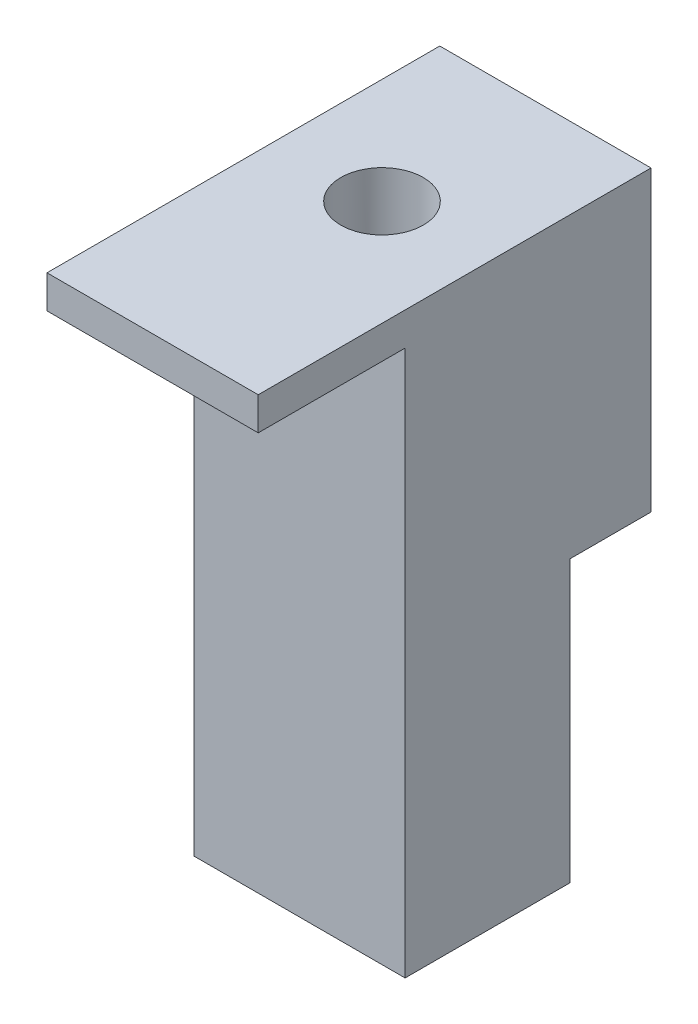
SolidWorks part; units mm, degrees
ref_plane "Front Plane" through (0, 0, 0) normal (0, 0, 1) x (1, 0, 0)
ref_plane "Top Plane" through (0, 0, 0) normal (0, 1, 0) x (1, 0, 0)
ref_plane "Right Plane" through (0, 0, 0) normal (1, 0, 0) x (0, 0, -1)
sketch "Sketch2" plane through (0, 0, 0) normal (0, 0, 1) x (1, 0, 0)
  line L0 (125.75, 12.9444) -> (138.75, 12.9444) construction
  line L5 (125.45, -3.5556) -> (138.75, -3.5556)
  line L6 (138.75, -3.5556) -> (138.75, 35)
  line L7 (138.75, 35) -> (125.75, 35)
  line L8 (125.75, 35) -> (125.75, 5.0019)
  line L9 (125.45, 3.05) -> (125.45, -3.5556)
  line L10 (125.45, -3.5556) -> (138.75, -3.5556) construction
  line L11 (138.75, 12.9444) -> (138.75, 35)
  line L12 (138.75, 35) -> (125.75, 35)
  line L13 (125.75, 35) -> (125.75, 12.9444)
  arc A0 (138.75, 12.9444) -> (125.75, 12.9444) centre (132.25, 12.9444) ccw
  arc A1 (125.75, 5.0019) -> (125.45, 3.05) centre (131.95, 3.05) ccw
  point P8 (132.25, 12.9444)
  dimension "D2" = 16.5
  dimension "D1" = 0
extrude "Boss-Extrude1" add sketch "Sketch2" along normal blind 10
sketch "Sketch3" plane through (0, 35, 0) normal (0, 1, 0) x (1, 0, 0)
  line L0 (138.75, -5) -> (125.75, -5)
  line L1 (138.75, -10) -> (138.75, 0) construction
  line L2 (125.75, -10) -> (125.75, 0) construction
  line L4 (138.75, -5) -> (125.75, -5)
  line L5 (138.75, -5) -> (138.75, -10)
  line L6 (138.75, -10) -> (125.75, -10)
  line L7 (125.75, -5) -> (125.75, -10)
  line M2 (125.75, 0) -> (125.75, -10)
  line M3 (125.75, -10) -> (138.75, -10)
  line M4 (138.75, -10) -> (138.75, 0)
extrude "Boss-Extrude2" add sketch "Sketch3" against normal up to vertex (22.0556 mm away) contours L0 M4 M2 M3 region at (132.25, 35, 7.5) up to point (138.75, 12.9444, 10)
sketch "Sketch4" plane through (0, 35, 0) normal (0, 1, 0) x (1, 0, 0)
  line L0 (125.75, 0) -> (125.75, -24) construction
  line L1 (138.75, -10) -> (125.75, -10)
  line L2 (138.75, -10) -> (138.75, -15)
  line L3 (138.75, -15) -> (125.75, -15)
  line L4 (125.75, -10) -> (125.75, -15)
  dimension "D1" = 5
extrude "Boss-Extrude3" add sketch "Sketch4" against normal up to vertex (22.0556 mm away) up to point (138.75, 12.9444, 10)
sketch "Sketch5" plane through (0, 12.9444, 0) normal (0, -1, 0) x (1, 0, 0)
  line L0 (125.75, 15) -> (138.75, 5) construction
  circle A0 centre (132.25, 10) radius 2.5
  dimension "D1" = 5
extrude "Cut-Extrude1" cut sketch "Sketch5" against normal blind 23
sketch "Sketch6" plane through (0, 12.9444, 0) normal (0, -1, 0) x (1, 0, 0)
  line L0 (138.75, 15) -> (138.75, 5) construction
  line L1 (125.75, 8.5) -> (138.75, 8.5)
  line L2 (125.75, 8.5) -> (125.75, 11.5)
  line L3 (125.75, 11.5) -> (138.75, 11.5)
  line L4 (138.75, 8.5) -> (138.75, 11.5)
  line L5 (125.75, 8.5) -> (138.75, 11.5) construction
  line L6 (125.75, 11.5) -> (138.75, 8.5) construction
  line L7 (127.25, 11.5) -> (127.25, 8.5)
  line L8 (137.25, 11.5) -> (137.25, 8.5)
  point P0 (132.25, 10)
  circle M4 centre (132.25, 10) radius 2.5
  dimension "D1" = 3
  dimension "D2" = 5
  dimension "D3" = 5
extrude "Cut-Extrude2" cut sketch "Sketch6" against normal offset from surface (17.0556 mm away) 5 contours L8 L3 L1 M4 | L3 L7 L1 M4 region at (128.5837, 12.9444, 10) region at (135.9163, 12.9444, 10) up to face at (132.25, 35, 7.5)
sketch "Sketch7" plane through (0, 12.9444, 0) normal (0, -1, 0) x (1, 0, 0)
  line L0 (132.25, 10) -> (132.25, 5)
  line L1 (131, 10) -> (133.5, 10)
  line L2 (131, 5) -> (133.5, 5)
  line L3 (133.5, 10) -> (133.5, 5)
  line L4 (138.75, 5) -> (125.75, 5) construction
  line L5 (131, 10) -> (131, 5)
  line M8 (125.75, 5) -> (138.75, 5)
  arc M12 (134.25, 8.5) -> (130.25, 8.5) centre (132.25, 10) cw
  dimension "D1" = 1.25
extrude "Cut-Extrude3" cut sketch "Sketch7" against normal blind 5 contours L5 L0 M12 M8 | L3 L0 M12 M8 region at (132.8882, 12.9444, 6.3061) region at (131.6118, 12.9444, 6.3061)
sketch "Sketch8" plane through (0, 12.9444, 0) normal (0, -1, 0) x (1, 0, 0)
  line L13 (133.5, 7.8349) -> (133.5, 5)
  line L14 (133.5, 5) -> (138.75, 5)
  line L15 (138.75, 5) -> (138.75, 15)
  line L16 (138.75, 15) -> (125.75, 15)
  line L17 (125.75, 15) -> (125.75, 5)
  line L18 (125.75, 5) -> (131, 5)
  line L19 (131, 5) -> (131, 7.8349)
  line L20 (130.25, 8.5) -> (127.25, 8.5)
  line L21 (127.25, 8.5) -> (127.25, 11.5)
  line L22 (127.25, 11.5) -> (130.25, 11.5)
  line L23 (134.25, 11.5) -> (137.25, 11.5)
  line L24 (137.25, 11.5) -> (137.25, 8.5)
  line L25 (137.25, 8.5) -> (134.25, 8.5)
  line L26 (133.5, 7.8349) -> (133.5, 5)
  line L27 (133.5, 5) -> (138.75, 5)
  line L28 (138.75, 5) -> (138.75, 15)
  line L29 (138.75, 15) -> (125.75, 15)
  line L30 (125.75, 15) -> (125.75, 5)
  line L31 (125.75, 5) -> (131, 5)
  line L32 (131, 5) -> (131, 7.8349)
  line L33 (130.25, 8.5) -> (127.25, 8.5)
  line L34 (127.25, 8.5) -> (127.25, 11.5)
  line L35 (127.25, 11.5) -> (130.25, 11.5)
  line L36 (134.25, 11.5) -> (137.25, 11.5)
  line L37 (137.25, 11.5) -> (137.25, 8.5)
  line L38 (137.25, 8.5) -> (134.25, 8.5)
  arc A3 (130.25, 8.5) -> (131, 7.8349) centre (132.25, 10) ccw
  arc A4 (134.25, 11.5) -> (130.25, 11.5) centre (132.25, 10) ccw
  arc A5 (133.5, 7.8349) -> (134.25, 8.5) centre (132.25, 10) ccw
  arc A6 (130.25, 8.5) -> (131, 7.8349) centre (132.25, 10) ccw
  arc A7 (134.25, 11.5) -> (130.25, 11.5) centre (132.25, 10) ccw
  arc A8 (133.5, 7.8349) -> (134.25, 8.5) centre (132.25, 10) ccw
  dimension "D1" = 0
extrude "Boss-Extrude4" add sketch "Sketch8" along normal blind 13
sketch "Sketch10" plane through (0, -0.0556, 0) normal (0, -1, 0) x (1, 0, 0)
  line L0 (125.75, 5) -> (125.75, 0) construction
  line L5 (138.75, 5) -> (138.75, 0) construction
  line L6 (125.75, 5) -> (125.75, 0)
  line L7 (138.75, 5) -> (138.75, 0)
  line L9 (125.75, 5) -> (138.75, 5)
  line L10 (125.75, 5) -> (125.75, 0)
  line L11 (125.75, 0) -> (138.75, 0)
  line L12 (138.75, 5) -> (138.75, 0)
  line M3 (133.5, 5) -> (138.75, 5)
  line M7 (125.75, 5) -> (131, 5)
extrude "Cut-Extrude4" cut sketch "Sketch10" against normal blind 17 contours L6 L11 L7 L9 M3 M7 region at (132.25, -0.0556, 2.5)
sketch "Sketch11" plane through (0, 35, 0) normal (0, 1, 0) x (1, 0, 0)
  line L0 (125.85, -0.1) -> (125.85, -23.9)
  line L1 (125.75, 0) -> (138.75, 0)
  line L2 (125.75, 0) -> (125.75, -24)
  line L3 (125.75, -24) -> (138.75, -24)
  line L4 (138.75, 0) -> (138.75, -24)
  line L5 (125.85, -23.9) -> (138.65, -23.9)
  line L6 (138.65, -0.1) -> (138.65, -23.9)
  line L7 (125.85, -0.1) -> (138.65, -0.1)
  circle A0 centre (132.25, -10) radius 2.5 construction
  circle A1 centre (132.25, -10) radius 2.5
  circle M9 centre (132.25, -10) radius 2.5
  line M12 (125.75, -15) -> (138.75, -15)
  dimension "D1" = 0.1
extrude "Boss-Extrude5" add sketch "Sketch11" against normal blind 2 contours L7 L0 L6 M12 M9 | L6 L0 L5 M12 region at (132.25, 35, 7.2688) region at (132.25, 35, 19.45)
sketch "Sketch12" plane through (0, 35, 0) normal (0, 1, 0) x (1, 0, 0)
  line L8 (138.65, -14.9) -> (138.65, -15)
  line L9 (125.85, -14.9) -> (125.85, -15)
  line L16 (138.55, -23.8) -> (138.55, -14.9)
  line L17 (138.55, -14.9) -> (138.65, -14.9)
  line L18 (138.65, -14.9) -> (138.65, -0.1)
  line L19 (138.65, -0.1) -> (125.85, -0.1)
  line L20 (125.85, -0.1) -> (125.85, -14.9)
  line L21 (125.85, -14.9) -> (125.95, -14.9)
  line L22 (125.95, -14.9) -> (125.95, -23.8)
  line L23 (125.95, -23.8) -> (138.55, -23.8)
  line L24 (138.55, -23.8) -> (138.55, -14.9)
  line L25 (138.55, -14.9) -> (138.65, -14.9)
  line L26 (138.65, -14.9) -> (138.65, -0.1)
  line L27 (138.65, -0.1) -> (125.85, -0.1)
  line L28 (125.85, -0.1) -> (125.85, -14.9)
  line L29 (125.85, -14.9) -> (125.95, -14.9)
  line L30 (125.95, -14.9) -> (125.95, -23.8)
  line L31 (125.95, -23.8) -> (138.55, -23.8)
  line L34 (138.65, -23.9) -> (138.65, -15)
  line L35 (138.65, -15) -> (138.75, -15)
  line L36 (138.75, -15) -> (138.75, 0)
  line L37 (138.75, 0) -> (125.75, 0)
  line L38 (125.75, 0) -> (125.75, -15)
  line L39 (125.75, -15) -> (125.85, -15)
  line L40 (125.85, -15) -> (125.85, -23.9)
  line L41 (125.85, -23.9) -> (138.65, -23.9)
  line L42 (138.65, -23.9) -> (138.65, -15)
  line L43 (138.65, -15) -> (138.75, -15)
  line L44 (138.75, -15) -> (138.75, 0)
  line L45 (138.75, 0) -> (125.75, 0)
  line L46 (125.75, 0) -> (125.75, -15)
  line L47 (125.75, -15) -> (125.85, -15)
  line L48 (125.85, -15) -> (125.85, -23.9)
  line L49 (125.85, -23.9) -> (138.65, -23.9)
  line M19 (138.65, -15) -> (138.75, -15)
  line M20 (138.75, -15) -> (138.75, 0)
  line M21 (138.75, 0) -> (125.75, 0)
  line M22 (125.75, 0) -> (125.75, -15)
  line M23 (125.75, -15) -> (125.85, -15)
  dimension "D1" = 0.1
  dimension "D2" = 0
extrude "Cut-Extrude5" cut sketch "Sketch12" against normal blind 37 contours L28 L27 L26 L8 L9 M19 M20 M21 M22 M23 region at (138.6698, 35, 7.5)
